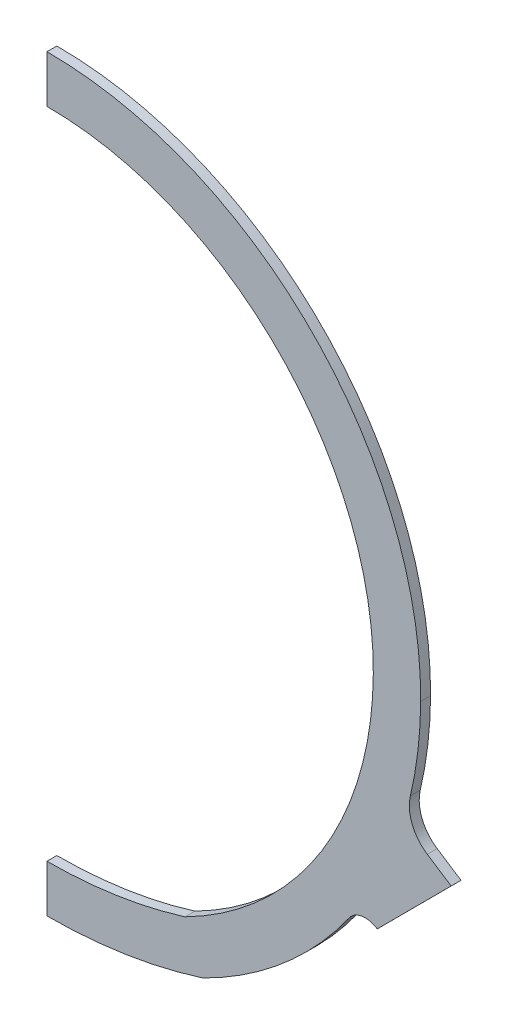
SolidWorks part; units mm, degrees
material "Balsa"
ref_plane "Front Plane" through (0, 0, 0) normal (0, 0, 1) x (1, 0, 0)
ref_plane "Top Plane" through (0, 0, 0) normal (0, 1, 0) x (1, 0, 0)
ref_plane "Right Plane" through (0, 0, 0) normal (1, 0, 0) x (0, 0, -1)
sketch "Sketch2" plane through (0, 0, 0) normal (0, 0, 1) x (1, 0, 0)
  line L0 (0, 0) -> (0.688, 245.4392) construction
  line L1 (-0.1309, -46.7153) -> (-0.2841, -101.3462) construction
  line L2 (0.0534, 19.05) -> (-169.3081, 19.05) construction
  line L3 (-72.7218, -93.726) -> (74.7111, -93.726) construction
  arc A1 (-120.0989, 19.05) -> (120.2036, 18.3433) centre (0.0534, 19.05) cw
  arc A2 (-120.0989, 19.05) -> (-50.0584, -93.726) centre (5.7147, 19.05) ccw
  arc A3 (-50.0584, -93.726) -> (50.1388, -93.726) centre (0.0402, 63.5) ccw
  arc A4 (120.2036, 18.3433) -> (50.1388, -93.726) centre (-5.6406, 19.0835) cw
  arc A5 (-104.8589, 19.05) -> (104.9639, 18.4329) centre (0.0534, 19.05) cw
  arc A6 (104.9639, 18.4329) -> (44.4049, -79.5534) centre (-5.6406, 19.0835) cw
  arc A7 (-44.324, -79.5535) -> (44.4049, -79.5534) centre (0.0402, 63.5) ccw
  arc A8 (-104.8589, 19.05) -> (-44.324, -79.5535) centre (5.7147, 19.05) ccw
  spline S0 degree 3 poles (-7457.5243, 7873.9786) (-1520.6447, 792.6716) (-232.684, -284.717) (69.4764, -82.4823) (75.8596, -77.7331) (81.7614, -72.3621) (85.2966, -68.8071) (85.996, -68.0862) (87.3792, -66.6243) (88.0639, -65.8824) (90.0847, -63.6371) (91.3894, -62.1126) (95.1787, -57.4581) (97.5389, -54.2471) (101.9343, -47.6137) (103.9694, -44.1914) (106.7765, -38.8981) (107.6712, -37.107) (109.3772, -33.4707) (110.1904, -31.6207) (112.481, -26.0415) (113.8153, -22.2742) (116.1105, -14.6467) (117.0712, -10.7866) (118.62, -2.9737) (119.208, 0.9791) (119.8028, 6.9796) (119.953, 8.9949) (120.1541, 13.0067) (120.2055, 15.0081) (120.2151, 20.9991) (119.8425, 28.9519) (118.7088, 36.835) (117.5685, 42.7208) (117.1399, 44.6783) (116.1841, 48.5842) (115.6559, 50.5346) (113.94, 56.3082) (112.6165, 60.0751) (109.6192, 67.4485) (107.9453, 71.055) (104.2453, 78.1066) (102.2192, 81.5518) (99.4588, 85.754) (98.8945, 86.5903) (97.7468, 88.2466) (97.1639, 89.0659) (95.3883, 91.4977) (94.1686, 93.0841) (90.4034, 97.7402) (87.752, 100.7072) (82.1689, 106.369) (79.2371, 109.0639) (74.6247, 112.8977) (73.0514, 114.1408) (70.6363, 115.9521) (69.821, 116.5478) (68.1799, 117.7153) (67.3537, 118.2875) (63.1947, 121.0918) (59.7778, 123.1535) (52.769, 126.9212) (49.1769, 128.6272) (41.816, 131.6806) (38.0473, 133.028) (33.2217, 134.4796) (32.2518, 134.758) (30.3116, 135.2882) (29.34, 135.5404) (26.4206, 136.2591) (24.4685, 136.6873) (18.5945, 137.8219) (14.6552, 138.3782) (6.7301, 139.0933) (2.7444, 139.252) (-2.2675, 139.1959) (-3.2714, 139.172) (-5.2821, 139.0983) (-6.2905, 139.0484) (-9.3072, 138.8606) (-11.3068, 138.6846) (-17.272, 138.0072) (-25.1357, 136.7069) (-32.823, 134.6274) (-38.5216, 132.7724) (-40.41, 132.1048) (-44.1641, 130.6694) (-46.0326, 129.9002) (-538.3584, -87.5727) (554.8292, -3549.2971) (3251.8348, -10297.372) knots -2.787439 -2.787439 -2.787439 -2.787439 0.03125 0.03125 0.0625 0.09375 0.09375 0.101563 0.101563 0.109375 0.109375 0.125 0.125 0.15625 0.15625 0.1875 0.1875 0.203125 0.203125 0.21875 0.21875 0.25 0.25 0.28125 0.28125 0.3125 0.3125 0.328125 0.328125 0.34375 0.34375 0.375 0.40625 0.40625 0.421875 0.421875 0.4375 0.4375 0.46875 0.46875 0.5 0.5 0.53125 0.53125 0.539063 0.539063 0.546875 0.546875 0.5625 0.5625 0.59375 0.59375 0.625 0.625 0.640625 0.640625 0.648438 0.648438 0.65625 0.65625 0.6875 0.6875 0.71875 0.71875 0.75 0.75 0.757813 0.757813 0.765625 0.765625 0.78125 0.78125 0.8125 0.8125 0.84375 0.84375 0.851563 0.851563 0.859375 0.859375 0.875 0.875 0.90625 0.9375 0.9375 0.953125 0.953125 0.96875 0.96875 5.126469 5.126469 5.126469 5.126469 only from (55.8537, -90.8749) to (-58.6671, 123.6507)
  spline S1 degree 3 poles (55.8537, -90.8749) (59.4151, -88.9779) (62.8499, -86.9173) (69.4764, -82.4823) (75.8596, -77.7331) (81.7614, -72.3621) (85.2966, -68.8071) (85.996, -68.0862) (87.3792, -66.6243) (88.0639, -65.8824) (90.0847, -63.6371) (91.3894, -62.1126) (95.1787, -57.4581) (97.5389, -54.2471) (101.9343, -47.6137) (103.9694, -44.1914) (106.7765, -38.8981) (107.6712, -37.107) (109.3772, -33.4707) (110.1904, -31.6207) (112.481, -26.0415) (113.8153, -22.2742) (116.1105, -14.6467) (117.0712, -10.7866) (118.62, -2.9737) (119.208, 0.9791) (119.8028, 6.9796) (119.953, 8.9949) (120.1541, 13.0067) (120.2055, 15.0081) (120.2151, 20.9991) (119.8425, 28.9519) (118.7088, 36.835) (117.5685, 42.7208) (117.1399, 44.6783) (116.1841, 48.5842) (115.6559, 50.5346) (113.94, 56.3082) (112.6165, 60.0751) (109.6192, 67.4485) (107.9453, 71.055) (104.2453, 78.1066) (102.2192, 81.5518) (99.4588, 85.754) (98.8945, 86.5903) (97.7468, 88.2466) (97.1639, 89.0659) (95.3883, 91.4977) (94.1686, 93.0841) (90.4034, 97.7402) (87.752, 100.7072) (82.1689, 106.369) (79.2371, 109.0639) (74.6247, 112.8977) (73.0514, 114.1408) (70.6363, 115.9521) (69.821, 116.5478) (68.1799, 117.7153) (67.3537, 118.2875) (63.1947, 121.0918) (59.7778, 123.1535) (52.769, 126.9212) (49.1769, 128.6272) (41.816, 131.6806) (38.0473, 133.028) (33.2217, 134.4796) (32.2518, 134.758) (30.3116, 135.2882) (29.34, 135.5404) (26.4206, 136.2591) (24.4685, 136.6873) (18.5945, 137.8219) (14.6552, 138.3782) (6.7301, 139.0933) (2.7444, 139.252) (-2.2675, 139.1959) (-3.2714, 139.172) (-5.2821, 139.0983) (-6.2905, 139.0484) (-9.3072, 138.8606) (-11.3068, 138.6846) (-17.272, 138.0072) (-25.1357, 136.7069) (-32.823, 134.6274) (-38.5216, 132.7724) (-40.41, 132.1048) (-44.1641, 130.6694) (-46.0326, 129.9002) (-51.5624, 127.4576) (-55.1595, 125.6458) (-58.6671, 123.6507) knots 0 0 0 0 0.03125 0.03125 0.0625 0.09375 0.09375 0.101563 0.101563 0.109375 0.109375 0.125 0.125 0.15625 0.15625 0.1875 0.1875 0.203125 0.203125 0.21875 0.21875 0.25 0.25 0.28125 0.28125 0.3125 0.3125 0.328125 0.328125 0.34375 0.34375 0.375 0.40625 0.40625 0.421875 0.421875 0.4375 0.4375 0.46875 0.46875 0.5 0.5 0.53125 0.53125 0.539063 0.539063 0.546875 0.546875 0.5625 0.5625 0.59375 0.59375 0.625 0.625 0.640625 0.640625 0.648438 0.648438 0.65625 0.65625 0.6875 0.6875 0.71875 0.71875 0.75 0.75 0.757813 0.757813 0.765625 0.765625 0.78125 0.78125 0.8125 0.8125 0.84375 0.84375 0.851563 0.851563 0.859375 0.859375 0.875 0.875 0.90625 0.9375 0.9375 0.953125 0.953125 0.96875 0.96875 1 1 1 1 construction
  spline S2 degree 3 poles (7698.4035, -7600.8615) (1611.4613, -764.0515) (222.821, 341.9355) (-76.9523, 111.0297) (-81.0984, 107.3558) (-85.9766, 102.3921) (-86.9369, 101.3807) (-88.8267, 99.3202) (-89.7577, 98.2691) (-92.4915, 95.0728) (-94.2304, 92.8907) (-99.2026, 86.1952) (-102.1931, 81.5333) (-106.1993, 74.2476) (-107.4545, 71.77) (-109.2154, 67.9791) (-109.782, 66.7031) (-110.874, 64.1258) (-111.4002, 62.8224) (-113.9097, 56.2871) (-115.5417, 50.9767) (-118.0823, 40.1978) (-118.9908, 34.7292) (-119.6657, 27.7928) (-119.7775, 26.4005) (-119.9543, 23.6055) (-120.0192, 22.2016) (-120.1418, 18.0057) (-120.1286, 15.2199) (-119.8102, 6.8959) (-119.2278, 1.3912) (-117.8014, -6.7994) (-117.2335, -9.5184) (-116.2404, -13.58) (-115.8858, -14.9311) (-115.1288, -17.6274) (-114.7258, -18.9739) (-112.6063, -25.6411) (-108.5276, -35.9696) (-103.1136, -45.6397) (-99.3011, -51.4722) (-98.5171, -52.628) (-96.9053, -54.9182) (-96.0765, -56.0537) (-93.5433, -59.4015) (-91.7865, -61.5635) (-86.3167, -67.8444) (-82.4051, -71.759) (-76.1398, -77.2217) (-73.9848, -78.9742) (-70.6503, -81.498) (-69.5218, -82.3217) (-67.2303, -83.9337) (-66.0665, -84.7222) (591.775, -513.8293) (4465.0583, 6093.4616) (-858.1872, -7414.6277) knots -4.145324 -4.145324 -4.145324 -4.145324 0.0625 0.0625 0.125 0.125 0.140625 0.140625 0.15625 0.15625 0.1875 0.1875 0.25 0.25 0.28125 0.28125 0.296875 0.296875 0.3125 0.3125 0.375 0.375 0.4375 0.4375 0.453125 0.453125 0.46875 0.46875 0.5 0.5 0.5625 0.5625 0.59375 0.59375 0.609375 0.609375 0.625 0.625 0.6875 0.75 0.75 0.765625 0.765625 0.78125 0.78125 0.8125 0.8125 0.875 0.875 0.90625 0.90625 0.921875 0.921875 0.9375 0.9375 9.693438 9.693438 9.693438 9.693438 only from (-58.6671, 123.6507) to (-50.3455, -93.5936)
  spline S3 degree 3 poles (-6093.8521, 8949.2565) (1657.017, -4470.2733) (1699.3783, -2108.1952) (-3189.6914, 10349.9889) knots -230.213154 -230.213154 -230.213154 -230.213154 248.242551 248.242551 248.242551 248.242551 only from (49.819, -93.8744) to (55.8537, -90.8749)
  spline S4 degree 3 poles (49.819, -93.8744) (51.8584, -92.9316) (53.87, -91.9317) (55.8537, -90.8749) knots 0 0 0 0 1 1 1 1 construction
  spline S5 degree 3 poles (-58.6671, 123.6507) (-63.5487, 120.874) (-68.1774, 117.7887) (-76.9523, 111.0297) (-81.0984, 107.3558) (-85.9766, 102.3921) (-86.9369, 101.3807) (-88.8267, 99.3202) (-89.7577, 98.2691) (-92.4915, 95.0728) (-94.2304, 92.8907) (-99.2026, 86.1952) (-102.1931, 81.5333) (-106.1993, 74.2476) (-107.4545, 71.77) (-109.2154, 67.9791) (-109.782, 66.7031) (-110.874, 64.1258) (-111.4002, 62.8224) (-113.9097, 56.2871) (-115.5417, 50.9767) (-118.0823, 40.1978) (-118.9908, 34.7292) (-119.6657, 27.7928) (-119.7775, 26.4005) (-119.9543, 23.6055) (-120.0192, 22.2016) (-120.1418, 18.0057) (-120.1286, 15.2199) (-119.8102, 6.8959) (-119.2278, 1.3912) (-117.8014, -6.7994) (-117.2335, -9.5184) (-116.2404, -13.58) (-115.8858, -14.9311) (-115.1288, -17.6274) (-114.7258, -18.9739) (-112.6063, -25.6411) (-108.5276, -35.9696) (-103.1136, -45.6397) (-99.3011, -51.4722) (-98.5171, -52.628) (-96.9053, -54.9182) (-96.0765, -56.0537) (-93.5433, -59.4015) (-91.7865, -61.5635) (-86.3167, -67.8444) (-82.4051, -71.759) (-76.1398, -77.2217) (-73.9848, -78.9742) (-70.6503, -81.498) (-69.5218, -82.3217) (-67.2303, -83.9337) (-66.0665, -84.7222) (-60.2073, -88.5441) (-55.3561, -91.2432) (-50.3455, -93.5936) knots 0 0 0 0 0.0625 0.0625 0.125 0.125 0.140625 0.140625 0.15625 0.15625 0.1875 0.1875 0.25 0.25 0.28125 0.28125 0.296875 0.296875 0.3125 0.3125 0.375 0.375 0.4375 0.4375 0.453125 0.453125 0.46875 0.46875 0.5 0.5 0.5625 0.5625 0.59375 0.59375 0.609375 0.609375 0.625 0.625 0.6875 0.75 0.75 0.765625 0.765625 0.78125 0.78125 0.8125 0.8125 0.875 0.875 0.90625 0.90625 0.921875 0.921875 0.9375 0.9375 1 1 1 1 construction
  spline S6 degree 3 poles (-2482.9215, 10606.6105) (134.4304, 111.18) (111.5262, -73.4925) (45.8458, -95.3665) (44.8322, -95.6594) (41.7708, -96.4587) (39.7032, -96.8873) (35.5384, -97.6293) (33.4392, -97.9405) (29.2422, -98.4783) (27.1412, -98.7049) (20.8322, -99.2882) (16.6185, -99.55) (8.1799, -99.8877) (3.9548, -99.9623) (-4.5058, -99.9387) (-8.734, -99.8405) (-17.1695, -99.4557) (-21.3793, -99.1705) (-27.6778, -98.553) (-29.7745, -98.3152) (-33.9608, -97.7556) (-36.0504, -97.4344) (-39.177, -96.8603) (-40.2191, -96.653) (-42.292, -96.1992) (-43.3225, -95.953) (-45.3676, -95.407) (-46.3821, -95.1076) (-112.5445, -72.6554) (-128.1138, 114.0017) (2927.5642, 10491.2531) knots -1.983598 -1.983598 -1.983598 -1.983598 0.03125 0.03125 0.0625 0.0625 0.125 0.125 0.1875 0.1875 0.25 0.25 0.375 0.375 0.5 0.5 0.625 0.625 0.75 0.75 0.8125 0.8125 0.875 0.875 0.90625 0.90625 0.9375 0.9375 0.96875 0.96875 3.000363 3.000363 3.000363 3.000363 only from (49.8185, -93.8746) to (-50.3451, -93.5938)
  spline S7 degree 3 poles (49.8185, -93.8746) (48.8452, -94.325) (47.8521, -94.6984) (45.8458, -95.3665) (44.8322, -95.6594) (41.7708, -96.4587) (39.7032, -96.8873) (35.5384, -97.6293) (33.4392, -97.9405) (29.2422, -98.4783) (27.1412, -98.7049) (20.8322, -99.2882) (16.6185, -99.55) (8.1799, -99.8877) (3.9548, -99.9623) (-4.5058, -99.9387) (-8.734, -99.8405) (-17.1695, -99.4557) (-21.3793, -99.1705) (-27.6778, -98.553) (-29.7745, -98.3152) (-33.9608, -97.7556) (-36.0504, -97.4344) (-39.177, -96.8603) (-40.2191, -96.653) (-42.292, -96.1992) (-43.3225, -95.953) (-45.3676, -95.407) (-46.3821, -95.1076) (-48.3867, -94.4274) (-49.3773, -94.0483) (-50.3451, -93.5938) knots 0 0 0 0 0.03125 0.03125 0.0625 0.0625 0.125 0.125 0.1875 0.1875 0.25 0.25 0.375 0.375 0.5 0.5 0.625 0.625 0.75 0.75 0.8125 0.8125 0.875 0.875 0.90625 0.90625 0.9375 0.9375 0.96875 0.96875 1 1 1 1 construction
  spline S8 degree 1 poles (44.4895, -82.3468) (49.8828, -79.6661) knots 0 0 1 1 construction
  spline S9 degree 1 poles (49.8828, -79.6661) (-52.388, 112.6115) knots 0 0 1 1 construction
  spline S10 degree 1 poles (-52.388, 112.6115) (-44.952, -82.0958) knots 0 0 1 1 construction
  spline S11 degree 3 poles (44.4895, -82.3468) (44.9451, -82.1361) (45.8533, -81.7084) (47.2062, -81.0479) (48.5497, -80.3682) (49.4396, -79.9022) (49.8828, -79.6661) knots 0 0 0 0 0.250007 0.500014 0.750021 1.000028 1.000028 1.000028 1.000028 construction
  spline S12 degree 3 poles (49.8828, -79.6661) (51.4682, -78.8216) (54.6039, -77.0481) (60.6329, -73.2256) (67.7713, -67.9145) (75.6946, -60.7068) (85.376, -49.946) (92.2499, -39.5527) (97.0635, -29.9209) (99.9774, -23.2906) (102.9687, -14.8438) (105.5551, -4.452) (106.8747, 4.4138) (107.4138, 11.642) (107.598, 18.8242) (107.1791, 27.7507) (105.6575, 38.3493) (103.0737, 48.9109) (99.5091, 59.0529) (95.0071, 68.7524) (90.4672, 76.4728) (86.3465, 82.4205) (79.7918, 90.9419) (71.0678, 99.805) (59.5047, 108.4813) (50.3361, 114.0108) (40.7123, 118.5824) (32.2831, 121.5955) (25.3334, 123.4944) (18.366, 125.0225) (9.571, 126.2643) (-1.0997, 126.6912) (-11.9104, 126.0185) (-22.4327, 124.2743) (-36.1547, 120.5693) (-46.1487, 116.1604) (-52.388, 112.6115) knots 0 0 0 0 0.015625 0.03125 0.0625 0.09375 0.125 0.1875 0.203125 0.21875 0.25 0.28125 0.3125 0.328125 0.34375 0.375 0.40625 0.4375 0.46875 0.5 0.53125 0.546875 0.5625 0.625 0.65625 0.6875 0.71875 0.75 0.765625 0.78125 0.8125 0.84375 0.875 0.90625 0.9375 1 1 1 1 construction
  spline S13 degree 3 poles (-52.388, 112.6115) (-54.5585, 111.3769) (-58.8261, 108.7475) (-66.8816, 102.9693) (-76.1597, 94.757) (-85.9932, 83.258) (-92.681, 72.8203) (-97.1816, 63.9424) (-101.112, 54.6656) (-104.776, 42.7383) (-106.8137, 30.488) (-107.4512, 20.4245) (-107.4028, 10.4189) (-106.3564, 0.5368) (-104.3212, -9.2152) (-101.5955, -18.9231) (-97.0158, -30.5128) (-90.9605, -41.334) (-85.1677, -49.567) (-78.8706, -57.3154) (-71.8665, -64.3232) (-64.1621, -70.5906) (-57.9948, -74.9291) (-51.5954, -78.7902) (-47.193, -81.0446) (-44.952, -82.0958) knots 0 0 0 0 0.03125 0.0625 0.125 0.1875 0.25 0.28125 0.3125 0.375 0.4375 0.46875 0.5 0.5625 0.59375 0.625 0.6875 0.75 0.78125 0.8125 0.875 0.90625 0.9375 0.96875 1 1 1 1 construction
  spline S14 degree 1 poles (44.4849, -82.3489) (-44.9469, -82.0982) knots 0 0 1 1 construction
  spline S15 degree 3 poles (44.4849, -82.3489) (44.3746, -82.3999) (44.1627, -82.4934) (43.6492, -82.7012) (42.8561, -82.9839) (41.7841, -83.3184) (40.2245, -83.7477) (38.1103, -84.2445) (35.4106, -84.7656) (32.6063, -85.224) (28.7759, -85.7537) (23.885, -86.2821) (17.9201, -86.7432) (11.8971, -87.0512) (5.8396, -87.2261) (-2.2666, -87.2864) (-10.3738, -87.0974) (-18.3985, -86.6419) (-24.3556, -86.1481) (-29.2377, -85.5934) (-33.056, -85.0443) (-35.8555, -84.5718) (-38.5671, -84.0318) (-40.6899, -83.5223) (-42.2517, -83.0828) (-43.3238, -82.7417) (-44.1147, -82.4546) (-44.6269, -82.2439) (-44.8373, -82.1497) (-44.9469, -82.0982) knots 0 0 0 0 0.007812 0.015625 0.03125 0.046875 0.0625 0.09375 0.125 0.15625 0.1875 0.25 0.3125 0.375 0.4375 0.5 0.625 0.6875 0.75 0.8125 0.84375 0.875 0.90625 0.9375 0.953125 0.96875 0.984375 0.992188 1 1 1 1 construction
  point P12 (-0.2802, -99.9505)
  dimension "D3" = 19.05
  dimension "D4" = 93.726
  dimension "D5" = 63.5
  dimension "D6" = 15.24
  dimension "D1" = 12.7
  dimension "D2" = 12.7
extrude "Boss-Extrude1" add sketch "Sketch2" along normal mid plane 3.175
sketch "Sketch3" plane through (0, 0, 0) normal (1, 0, 0) x (0, 0, -1)
  line L1 (-100.0568, 212.3798) -> (108.5889, 212.3798)
  line L2 (-100.0568, 212.3798) -> (-100.0568, -170.6472)
  line L3 (-100.0568, -170.6472) -> (108.5889, -170.6472)
  line L4 (108.5889, 212.3798) -> (108.5889, -170.6472)
extrude "Cut-Extrude1" cut sketch "Sketch3" against normal through all
sketch "Sketch5" plane through (0, 0, 0) normal (0, 0, 1) x (1, 0, 0)
  line L0 (0, 0) -> (196.1994, 0) construction
  line L1 (106.2582, -51.9887) -> (130.0117, -28.1684)
  line L2 (130.0117, -28.1684) -> (114.5738, -18.1429)
  line L3 (106.2582, -51.9887) -> (100.047, -49.2352)
  line L4 (100.047, -49.2352) -> (114.5738, -18.1429)
  arc A0 (50.1388, -93.726) -> (120.2036, 18.3433) centre (-5.6406, 19.0835) ccw construction
  dimension "D1" = 33
  dimension "D2" = 18.1429
  dimension "D3" = 78.08
  dimension "D4" = 18.4076
  dimension "D6" = 33.6398
  dimension "D7" = 6.7941
extrude "Boss-Extrude2" add sketch "Sketch5" along normal mid plane 3.175
fillet "Fillet1" radius 6.35 1 edges at (100.047, -49.2352, 0)
fillet "Fillet2" radius 12.7 1 edges at (114.5738, -18.1429, 0)
